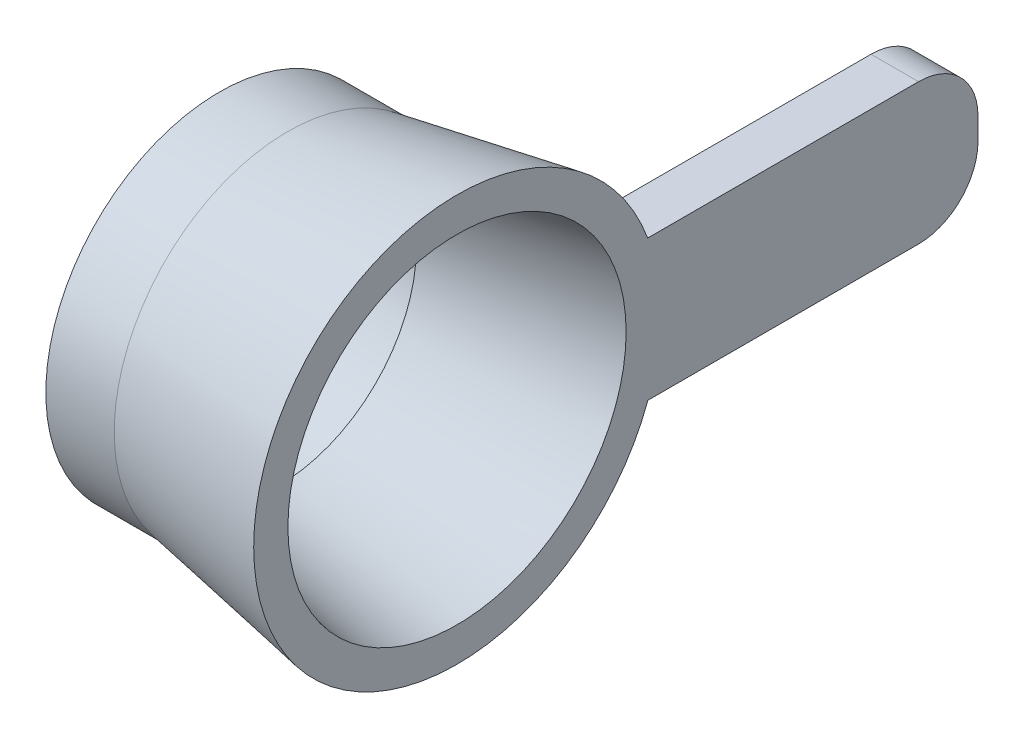
SolidWorks part; units mm, degrees
ref_plane "Front Plane" through (0, 0, 0) normal (0, 0, 1) x (1, 0, 0)
ref_plane "Top Plane" through (0, 0, 0) normal (0, 1, 0) x (1, 0, 0)
ref_plane "Right Plane" through (0, 0, 0) normal (1, 0, 0) x (0, 0, -1)
sketch "Sketch1" plane through (0, 0, 0) normal (1, 0, 0) x (0, 0, -1)
  circle A0 centre (0, 0) radius 12.5
  circle A1 centre (0, 0) radius 14.5945
extrude "Boss-Extrude1" add sketch "Sketch1" along normal blind 5
sketch "Sketch2" plane through (5, 0, 0) normal (1, 0, 0) x (0, 0, -1)
  circle A0 centre (0, 0) radius 11.2283
  circle A1 centre (0, 0) radius 17.4615
extrude "Boss-Extrude2" add sketch "Sketch2" along normal blind 15
chamfer "Chamfer1" distance 3 angle 80 1 edges at (5, 0, -17.4615) first distance on face at (5, 0, -14.5945)
chamfer "Chamfer2" distance 3 angle 80 1 edges at (20, 0, -11.2283) first distance on face at (20, 0, -17.1064)
sketch "Sketch3" plane through (20, 0, 0) normal (1, 0, 0) x (0, 0, -1)
  line L1 (15.6161, 5.9334) -> (43.833, 5.9334)
  line L2 (15.6161, 5.9334) -> (15.6161, -5.897)
  line L3 (15.6161, -5.897) -> (43.833, -5.897)
  line L4 (43.833, 5.9334) -> (43.833, -5.897)
extrude "Boss-Extrude3" add sketch "Sketch3" against normal blind 4
fillet "Fillet1" radius 5 2 edges at (18, 5.9334, -43.833) (18, -5.897, -43.833)
sketch "Sketch4" plane through (16, 0, 0) normal (-1, 0, 0) x (0, 0, 1)
  circle A0 centre (-37.3413, 0) radius 2.5359
  point P2 (-37.3413, 0)
extrude "Cut-Extrude1" cut sketch "Sketch4" against normal blind 3
